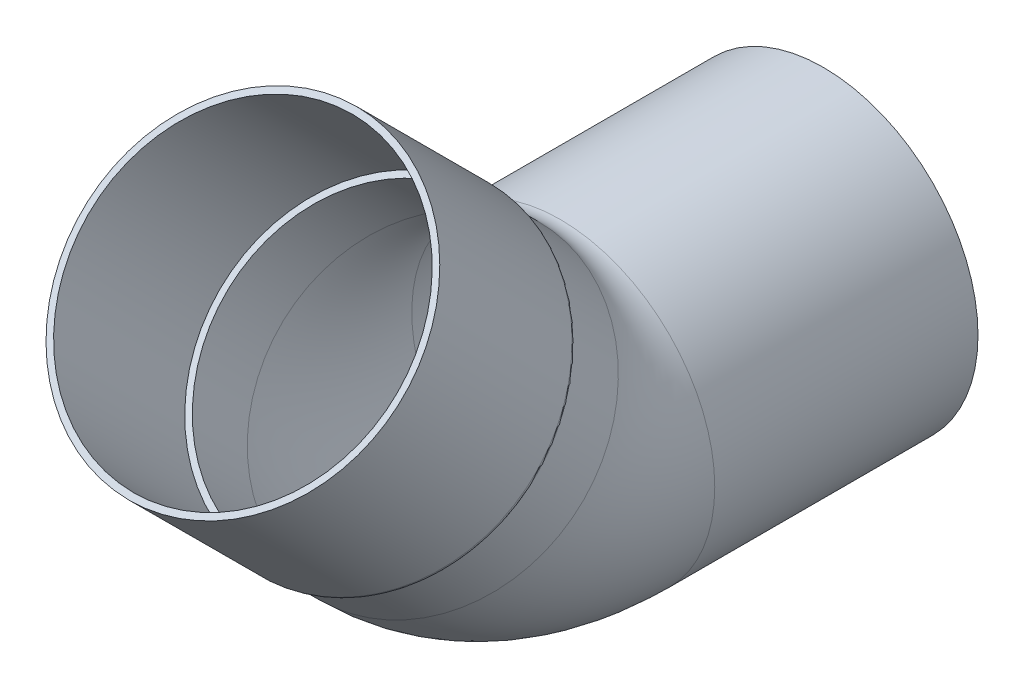
SolidWorks part; units mm, degrees
ref_plane "Plan de face" through (0, 0, 0) normal (0, 0, 1) x (1, 0, 0)
ref_plane "Plan de dessus" through (0, 0, 0) normal (0, 1, 0) x (1, 0, 0)
ref_plane "Plan de droite" through (0, 0, 0) normal (1, 0, 0) x (0, 0, -1)
sketch "Esquisse6" plane through (0, 0, 0) normal (0, 0, 1) x (1, 0, 0)
  circle A0 centre (0, 0) radius 25
sketch "Esquisse7" plane through (0, 0, 0) normal (1, 0, 0) x (0, 0, -1)
  line L0 (0, 0) -> (-42.5736, 0)
  line L1 (-63.7868, 8.7868) -> (-71.9706, 16.9706)
  arc A0 (-42.5736, 0) -> (-63.7868, 8.7868) centre (-42.5736, 30) cw
  point P6 (-55, 0)
  dimension "D4" = 30
  dimension "D1" = 24
  dimension "D2" = 55
  dimension "D3" = 45
sweep "Balayage-Mince2" add profiles "Esquisse6" path "Esquisse7" parameters "D1"=1
sketch "Esquisse8" plane through (0, 44.4706, 44.4706) normal (0, 0.7071, 0.7071) x (1, 0, 0)
  line L0 (-24, -38.8909) -> (24, -38.8909) construction
  line L1 (0, -14.8909) -> (0, -62.8909) construction
  circle A0 centre (0, -38.8909) radius 24 construction
  circle A1 centre (0, -38.8909) radius 24 construction
  circle A2 centre (0, -38.8909) radius 24
  point P10 (0, -38.8909)
extrude "Extru.-Mince1" add sketch "Esquisse8" along normal blind 1 separate body thin contours A2 thin type one direction wall 2
sketch "Esquisse9" plane through (0, 45.1777, 45.1777) normal (0, 0.7071, 0.7071) x (1, 0, 0)
  line L0 (-24, -38.8909) -> (24, -38.8909) construction
  line L1 (0, -14.8909) -> (0, -62.8909) construction
  circle A0 centre (0, -38.8909) radius 24 construction
  circle A1 centre (0, -38.8909) radius 24 construction
  circle A2 centre (0, -38.8909) radius 26
extrude "Extru.-Mince2" add sketch "Esquisse9" along normal blind 30 thin thin type one direction reverse wall 1
fillet "Congé1" radius 1 1 edges at (25, 16.9706, 71.9706)
fillet "Congé2" radius 1 1 edges at (26, 16.9706, 71.9706)
